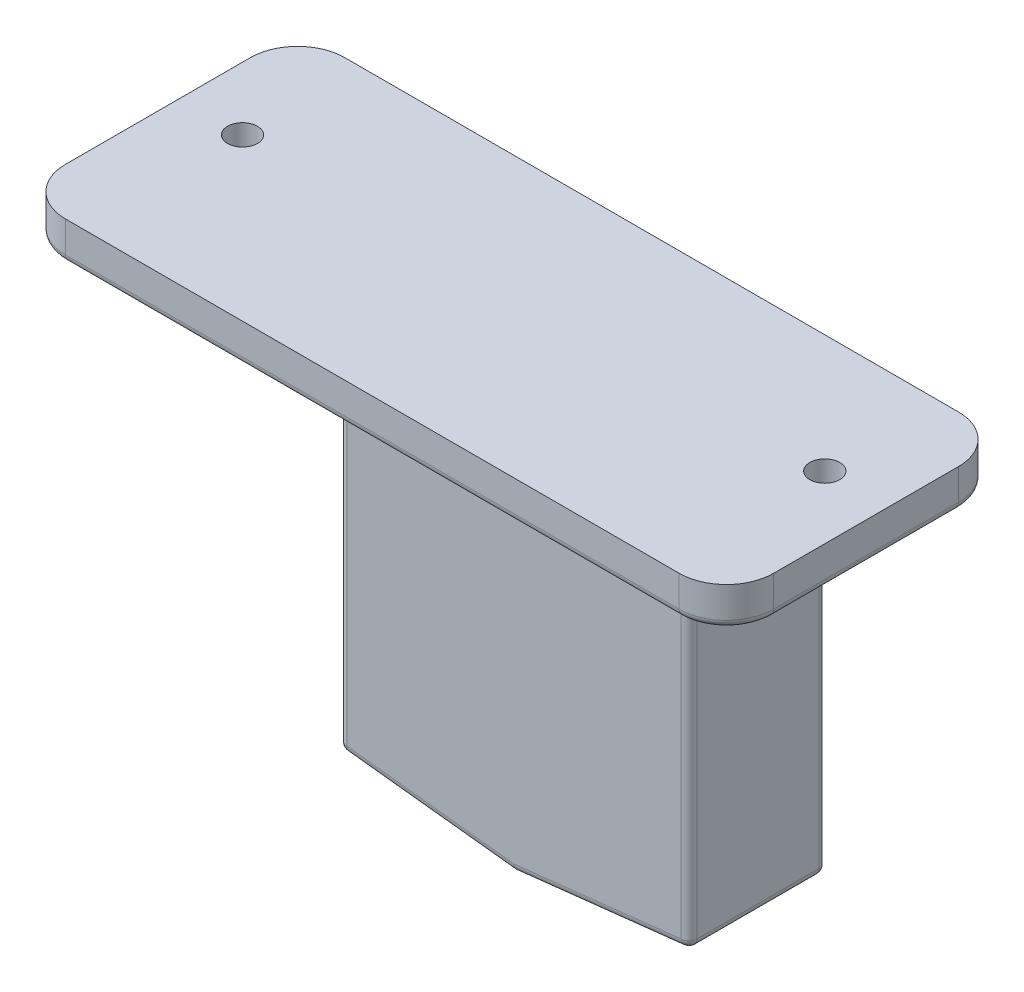
SolidWorks part; units mm, degrees
ref_plane "Ebene vorne" through (0, 0, 0) normal (0, 0, 1) x (1, 0, 0)
ref_plane "Ebene oben" through (0, 0, 0) normal (0, 1, 0) x (1, 0, 0)
ref_plane "Ebene rechts" through (0, 0, 0) normal (1, 0, 0) x (0, 0, -1)
sketch "Skizze1" plane through (0, 0, 0) normal (0, 0, 1) x (1, 0, 0)
  line L4 (0, 42.458) -> (0, -101.4826) construction
  line L5 (12.8101, -3.4356) -> (20.25, -4.2623)
  line L6 (20.25, -4.2623) -> (20.25, -54.7623)
  line L7 (20.25, -29.5123) -> (-20.25, -29.5123) construction
  line L8 (12.8101, -55.589) -> (20.25, -54.7623)
  line L9 (-12.8101, -55.589) -> (-20.25, -54.7623)
  line L10 (-20.25, -4.2623) -> (-20.25, -54.7623)
  line L11 (-12.8101, -3.4356) -> (-20.25, -4.2623)
  line L12 (0, 0) -> (122.9392, 0) construction
  line L13 (0, 0) -> (22.25, -2.4722)
  line L14 (22.25, -2.4722) -> (22.25, -56.5524)
  line L15 (0, -59.0246) -> (22.25, -56.5524)
  line L16 (0, -59.0246) -> (-22.25, -56.5524)
  line L17 (-22.25, -2.4722) -> (-22.25, -56.5524)
  line L18 (0, 0) -> (-22.25, -2.4722)
  line L19 (0, -2.0123) -> (20.25, -4.2623) construction
  line L20 (0, -2.0123) -> (-20.25, -4.2623) construction
  line L21 (0, -57.0123) -> (20.25, -54.7623) construction
  line L22 (0, -57.0123) -> (-20.25, -54.7623) construction
  line L24 (-45, -2.4722) -> (45, -2.4722)
  line L25 (-45, -2.4722) -> (-45, 2.4722)
  line L26 (-45, 2.4722) -> (45, 2.4722)
  line L27 (45, -2.4722) -> (45, 2.4722)
  line L28 (-45, -2.4722) -> (45, 2.4722) construction
  line L29 (-45, 2.4722) -> (45, -2.4722) construction
  arc A0 (12.8101, -3.4356) -> (-12.8101, -3.4356) centre (0, -118.7262) ccw
  arc A1 (12.8101, -55.589) -> (-12.8101, -55.589) centre (0, 59.7015) cw
  point P4 (0, -29.5123)
  point P33 (0, -2.0123)
  point P37 (0, -57.0123)
  dimension "D4" = 116
  dimension "D6" = 116
  dimension "D1" = 55
  dimension "D2" = 40.5
  dimension "D3" = 50.5
  dimension "D5" = 2
  dimension "D7" = 90
extrude "Aufsatz-Linear austragen1" add sketch "Skizze1" against normal blind 15 contours L17 | L13 L18 L17 L16 L15 L14 L11 L5 L6 L8 L9 L10 | L25 L24 L27 L26 | A1 L8 L6 L5 A0 L11 L10 L9 region at (21.5304, -29.5123, 0)
sketch "Skizze4" plane through (0, 0, -15) normal (0, 0, -1) x (-1, 0, 0)
  line L0 (12.8101, -3.4356) -> (20.25, -4.2623) construction
  line L1 (-12.8101, -3.4356) -> (-20.25, -4.2623) construction
  line L2 (-20.25, -4.2623) -> (-20.25, -54.7623) construction
  line L3 (-12.8101, -55.589) -> (-20.25, -54.7623) construction
  line L4 (12.8101, -55.589) -> (20.25, -54.7623) construction
  line L5 (20.25, -4.2623) -> (20.25, -54.7623) construction
  line L6 (12.8101, -3.4356) -> (20.25, -4.2623)
  line L7 (-12.8101, -3.4356) -> (-20.25, -4.2623)
  line L8 (-20.25, -4.2623) -> (-20.25, -54.7623)
  line L9 (-12.8101, -55.589) -> (-20.25, -54.7623)
  line L10 (12.8101, -55.589) -> (20.25, -54.7623)
  line L11 (20.25, -4.2623) -> (20.25, -54.7623)
  arc A0 (12.8101, -3.4356) -> (-12.8101, -3.4356) centre (0, -118.7262) ccw construction
  arc A1 (-12.8101, -55.589) -> (12.8101, -55.589) centre (0, 59.7015) ccw construction
  arc A2 (12.8101, -3.4356) -> (-12.8101, -3.4356) centre (0, -118.7262) ccw
  arc A3 (-12.8101, -55.589) -> (12.8101, -55.589) centre (0, 59.7015) ccw
extrude "Schnitt-Linear austragen5" cut sketch "Skizze4" against normal blind 20.5 draft 4
extrude "Aufsatz-Linear austragen4" add sketch "Skizze1<6>" along normal blind 2.5 contours L18 L24 L13 | L24 L27 L26 L25 L18 L13 | A1 L8 L6 L5 A0 L11 L10 L9 | L24 L17 L16 L15 L14 L8 A1 L9 L10 L11 A0 L5 L6 region at (0, -29.5123, 0) region at (0, 0.2325, 0) region at (0, -1.6481, 0) region at (21.5304, -29.5123, 0)
sketch "Skizze1<6>" plane through (0, 0, 0) normal (0, 0, 1) x (1, 0, 0) same geometry as "Skizze1"
extrude "Aufsatz-Linear austragen5" add sketch "Skizze1<7>" along normal blind 20.5 contours L24 L27 L26 L25 L18 L13 | L18 L24 L13 region at (0, 0.2325, 0) region at (0, -1.6481, 0)
sketch "Skizze1<7>" plane through (0, 0, 0) normal (0, 0, 1) x (1, 0, 0) same geometry as "Skizze1"
fillet "Verrundung1" radius 8 3 edges at (22.25, -2.4722, -6.25) (0, -2.4722, 2.5) (-22.25, -2.4722, -6.25)
fillet "Verrundung2" radius 6 4 edges at (45, 0, -15) (-45, 0, -15) (45, 0, 20.5) (-45, 0, 20.5)
fillet "Verrundung3" radius 1 23 edges at (-24.5931, -4.8154, 4.8431) (24.5931, -4.8154, 4.8431) (-22.25, -33.5123, -15) (-24.5931, -4.8154, -15) (-34.625, -2.4722, -15) (-43.2426, -2.4722, -13.2426) (-45, -2.4722, 2.75) (-43.2426, -2.4722, 18.7426) (22.25, -33.5123, -15) (24.5931, -4.8154, -15) (34.625, -2.4722, -15) (43.2426, -2.4722, -13.2426) (45, -2.4722, 2.75) (43.2426, -2.4722, 18.7426) (11.125, -57.7885, 2.5) (-11.125, -57.7885, 2.5) (-22.25, -33.5123, 2.5) (22.25, -33.5123, 2.5) (11.125, -57.7885, -15) (-11.125, -57.7885, -15) (0, -2.4722, 20.5) (22.25, -56.5524, -6.25) (-22.25, -56.5524, -6.25)
hole_wizard "Ø3.8 (3.8) Durchmesser Bohrung1" positions "3D-Skizze1" profile "Skizze3" hole size "Ø3.8" standard "ISO" end condition through all
sketch3d "3D-Skizze1"
  point P0 (-37, -2.4722, 0)
  point P3 (0, 0, 0)
  point P16 (0, 0, 0)
  point P21 (-37, -2.4722, 5.2554)
  point P22 (-37, -2.4722, 3.5368)
  point P25 (0, 0, 0)
  point P26 (37, -2.4722, 0)
  dimension "D1" = 8
  dimension "D2" = 15
sketch "Skizze3" plane through (-37, -2.4722, 0) normal (1, 0, 0) x (0, 0, -1)
  line L0 (0, 0) -> (0, 4.9444)
  line L1 (0, 4.9444) -> (1.9, 4.9444)
  line L2 (1.9, 4.9444) -> (1.9, 0)
  line L5 (1.9, 0) -> (0, 0)
  line L11 (0, -6.35) -> (0, 107.95) construction
  dimension "Bohrerdurchmesser" = 3.8
  dimension "Bohrungstiefe" = 4.9444
